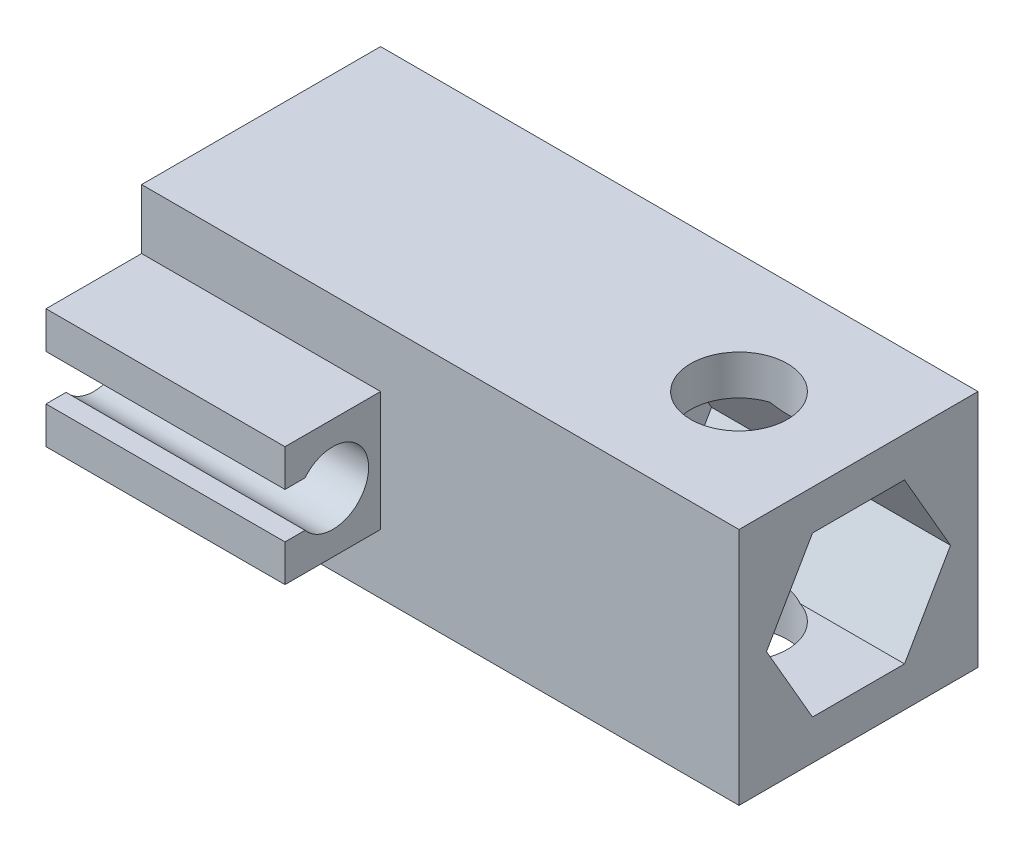
SolidWorks part; units mm, degrees
ref_plane "Спереди" through (0, 0, 0) normal (0, 0, 1) x (1, 0, 0)
ref_plane "Сверху" through (0, 0, 0) normal (0, 1, 0) x (1, 0, 0)
ref_plane "Справа" through (0, 0, 0) normal (1, 0, 0) x (0, 0, -1)
sketch "Sketch1" plane through (0, 0, 0) normal (0, 1, 0) x (1, 0, 0)
  line L0 (-25, 0) -> (25, 0) construction
  line L1 (25, -10) -> (-25, -10)
  line L2 (25, -10) -> (25, 10)
  line L3 (25, 10) -> (-25, 10)
  line L4 (-25, -10) -> (-25, 10)
  line L5 (25, -10) -> (-25, 10) construction
  line L6 (25, 10) -> (-25, -10) construction
  circle A0 centre (15, 0) radius 4.05
  point P0 (0, 0)
  dimension "D3" = 8.1
  dimension "D1" = 20
  dimension "D2" = 50
  dimension "D4" = 10
extrude "Boss-Extrude1" add sketch "Sketch1" along normal blind 20
sketch "Sketch2" plane through (-25, 0, 0) normal (-1, 0, 0) x (0, 0, 1)
  line L0 (0, 20) -> (0, 0) construction
  line L1 (-10, 20) -> (10, 20) construction
  line L2 (-10, 0) -> (10, 0) construction
  line L4 (5.05, 4.95) -> (-5.05, 4.95) construction
  line L5 (5.05, 4.95) -> (5.05, 15.05) construction
  line L6 (5.05, 15.05) -> (-5.05, 15.05) construction
  line L7 (-5.05, 4.95) -> (-5.05, 15.05) construction
  line L8 (5.05, 4.95) -> (-5.05, 15.05) construction
  line L9 (5.05, 15.05) -> (-5.05, 4.95) construction
  circle A0 centre (0, 10) radius 4.1
  point P6 (0, 10)
  dimension "D2" = 8.2
  dimension "D1" = 10.1
extrude "Cut-Extrude1" cut sketch "Sketch2" against normal through all
sketch "Sketch3" plane through (25, 0, 0) normal (1, 0, 0) x (0, 0, -1)
  line L0 (-10, 20) -> (10, 20) construction
  line L1 (-3.85, 16.6684) -> (-7.7, 10)
  line L2 (-7.7, 10) -> (-3.85, 3.3316)
  line L3 (-3.85, 3.3316) -> (3.85, 3.3316)
  line L4 (3.85, 3.3316) -> (7.7, 10)
  line L5 (7.7, 10) -> (3.85, 16.6684)
  line L6 (3.85, 16.6684) -> (-3.85, 16.6684)
  circle A0 centre (0, 10) radius 7.7 construction
  dimension "D1" = 15.4
extrude "Cut-Extrude2" cut sketch "Sketch3" against normal blind 20
sketch "Sketch8" plane through (-25, 0, 0) normal (-1, 0, 0) x (0, 0, 1)
  line L0 (10, 10) -> (18, 10) construction
  line L1 (10, 20) -> (10, 0) construction
  line L2 (18, 15) -> (18, 11.9)
  line L3 (18, 5) -> (10, 5)
  line L4 (18, 5) -> (18, 15) construction
  line L5 (18, 15) -> (10, 15)
  line L6 (10, 5) -> (10, 15)
  line L7 (18, 5) -> (10, 15) construction
  line L8 (18, 15) -> (10, 5) construction
  line L9 (18, 11.9) -> (16.3216, 11.9)
  line L10 (16.3216, 8.1) -> (18, 8.1)
  line L11 (18, 8.1) -> (18, 5)
  circle A0 centre (14, 10) radius 3 construction
  arc A1 (16.3216, 11.9) -> (16.3216, 8.1) centre (14, 10) ccw
  point P5 (14, 10)
  dimension "D1" = 6
  dimension "D2" = 3.8
  dimension "D3" = 8
  dimension "D4" = 10
extrude "Boss-Extrude3" add sketch "Sketch8" against normal blind 20
